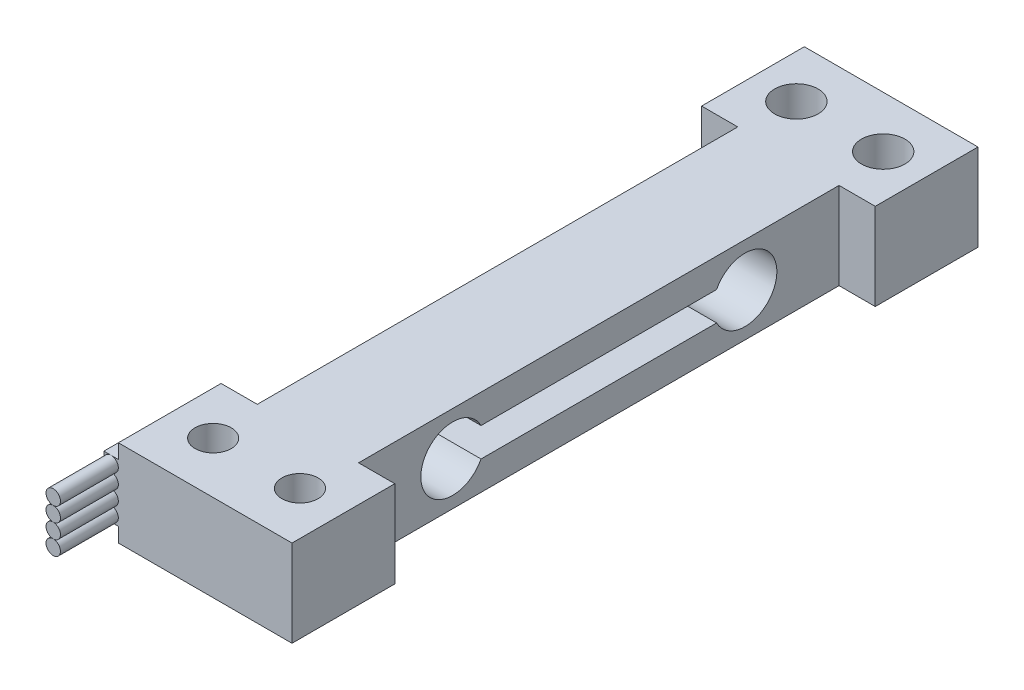
SolidWorks part; units mm, degrees
material "6063-O"
ref_plane "Front Plane" through (0, 0, 0) normal (0, 0, 1) x (1, 0, 0)
ref_plane "Top Plane" through (0, 0, 0) normal (0, 1, 0) x (1, 0, 0)
ref_plane "Right Plane" through (0, 0, 0) normal (1, 0, 0) x (0, 0, -1)
sketch "Sketch1" plane through (0, 0, 0) normal (0, 1, 0) x (1, 0, 0)
  line L0 (2.5, 7.1) -> (2.5, 40.3)
  line L1 (0, 0) -> (12, 0)
  line L2 (0, 0) -> (0, 7.1)
  line L3 (0, 7.1) -> (2.5, 7.1)
  line L4 (12, 0) -> (12, 7.1)
  line L5 (9.5, 7.1) -> (9.5, 40.3)
  line L6 (9.5, 40.3) -> (12, 40.3)
  line L7 (0, 40.3) -> (2.5, 40.3)
  line L8 (0, 40.3) -> (0, 47.4)
  line L9 (0, 47.4) -> (12, 47.4)
  line L10 (12, 40.3) -> (12, 47.4)
  line L11 (9.5, 7.1) -> (12, 7.1)
  point P13 (6, 0)
  dimension "D1" = 12
  dimension "D2" = 7.1
  dimension "D3" = 47.4
  dimension "D4" = 7
  dimension "D5" = 3.5
extrude "Boss-Extrude1" add sketch "Sketch1" along normal blind 6
sketch "Sketch2" plane through (0, 6, 0) normal (0, 1, 0) x (1, 0, 0)
  line L0 (12, 47.4) -> (0, 47.4) construction
  line L1 (0, 0) -> (12, 0) construction
  point P0 (3, 43.85)
  point P1 (9, 43.85)
  point P2 (9, 3.55)
  point P3 (3, 3.55)
  point P6 (6, 47.4)
  point P8 (6, 0)
  dimension "D1" = 6
  dimension "D2" = 3
  dimension "D3" = 3.55
  dimension "D4" = 6
  dimension "D5" = 3.55
  dimension "D6" = 3
hole_wizard "Ø3.0mm Dowel Hole1" positions "3DSketch1" profile "Sketch3" hole size "Ø3.0" standard "ISO" end condition through all
sketch3d "3DSketch1"
  point P0 (3, 6, -43.85)
  point P3 (9, 6, -43.85)
sketch "Sketch3" plane through (3, 6, -43.85) normal (1, 0, 0) x (0, 0, 1)
  line L0 (0, 0) -> (0, 6)
  line L1 (0, 6) -> (1.5, 6)
  line L2 (1.5, 6) -> (1.5, 0)
  line L5 (1.5, 0) -> (0, 0)
  line L11 (0, -6.35) -> (0, 107.95) construction
  dimension "Thru Hole Dia." = 3
  dimension "Thru Hole Depth" = 6
hole_wizard "Tap Drill for M3 Tap1" positions "3DSketch2" profile "Sketch4" hole size "M3" standard "ISO" end condition through all
sketch3d "3DSketch2"
  point P0 (9, 6, -3.55)
  point P3 (3, 6, -3.55)
sketch "Sketch4" plane through (9, 6, -3.55) normal (1, 0, 0) x (0, 0, 1)
  line L0 (0, 0) -> (0, 6)
  line L1 (0, 6) -> (1.25, 6)
  line L2 (1.25, 6) -> (1.25, 0)
  line L5 (1.25, 0) -> (0, 0)
  line L11 (0, -6.35) -> (0, 107.95) construction
  dimension "Thru Hole Dia." = 2.5
  dimension "Thru Hole Depth" = 6
sketch "Sketch5" plane through (0, 0, -47.4) normal (0, 0, -1) x (-1, 0, 0)
  line L0 (-6.75, 5) -> (-5.25, 5)
  line L1 (-5.25, 5) -> (-5.25, 2.68)
  line L2 (-5.25, 2.68) -> (-4, 2.68)
  line L3 (-4, 2.68) -> (-6, 1)
  line L4 (-6, 1) -> (-8, 2.68)
  line L5 (-8, 2.68) -> (-6.75, 2.68)
  line L6 (-6.75, 2.68) -> (-6.75, 5)
  line L7 (-12, 6) -> (0, 6) construction
  line L8 (-12, 0) -> (0, 0) construction
  point P8 (-6, 5)
  point P12 (-6, 6)
  dimension "D2" = 1
  dimension "D3" = 1.5
  dimension "D4" = 0.75
  dimension "D5" = 1.25
  dimension "D6" = 1.25
extrude "Boss-Extrude2" add sketch "Sketch5" along normal blind 0.25
sketch "Sketch6" plane through (9.5, 0, 0) normal (1, 0, 0) x (0, 0, -1)
  line L0 (47.4, 6) -> (47.4, 0) construction
  line L1 (0, 6) -> (0, 0) construction
  line L2 (15.5596, 4) -> (31.8404, 4)
  line L3 (15.5596, 2) -> (31.8404, 2)
  line L4 (7.1, 0) -> (40.3, 0) construction
  line L5 (7.1, 6) -> (40.3, 6) construction
  arc A0 (15.5596, 4) -> (15.5596, 2) centre (13.6, 3) ccw
  arc A1 (31.8404, 2) -> (31.8404, 4) centre (33.8, 3) ccw
  dimension "D1" = 4.4
  dimension "D2" = 13.6
  dimension "D3" = 13.6
  dimension "D4" = 2
  dimension "D5" = 2
extrude "Cut-Extrude1" cut sketch "Sketch6" against normal up to next
sketch "Sketch7" plane through (0, 0, 0) normal (-1, 0, 0) x (0, 0, 1)
  line L0 (0, 6) -> (0, 0) construction
  line L1 (0, 5) -> (-4.6, 5)
  line L2 (0, 5) -> (0, 1)
  line L3 (0, 1) -> (-4.6, 1)
  line L4 (-4.6, 5) -> (-4.6, 1)
  line L5 (-7.1, 6) -> (0, 6) construction
  line L6 (-7.1, 0) -> (0, 0) construction
  line L7 (-7.1, 6) -> (-7.1, 0) construction
  point P10 (-4.6, 3)
  dimension "D1" = 1
  dimension "D2" = 1
  dimension "D3" = 2.5
extrude "Boss-Extrude3" add sketch "Sketch7" along normal blind 1
sketch "Sketch8" plane through (0, 0, 0) normal (0, 0, 1) x (1, 0, 0)
  line L0 (-1, 1) -> (-1, 5) construction
  line L1 (-1, 5) -> (0, 5) construction
  circle A0 centre (-0.5, 4.5) radius 0.5
  circle A1 centre (-0.5, 3.5) radius 0.5
  circle A2 centre (-0.5, 2.5) radius 0.5
  circle A3 centre (-0.5, 1.5) radius 0.5
  dimension "D1" = 1
  dimension "D2" = 0.5
  dimension "D3" = 0.5
  dimension "D4" = 4
extrude "Boss-Extrude5" add sketch "Sketch8" along normal blind 4 separate body contours A0 | A1 | A2 | A3 region at (-0.5, 4.5, 0) region at (-0.5, 1.5, 0) region at (-0.5, 2.5, 0) region at (-0.5, 3.5, 0)
ref_plane "Plane1" through (6, 0, 0) normal (1, 0, 0) x (0, 0, -1)
ref_axis "Axis1" through (9, 0, -43.85) along (0, 1, 0)
ref_axis "Axis2" through (3, 0, -43.85) along (0, 1, 0)
ref_plane "Plane2" through (0, 0, -43.85) normal (0, 0, -1) x (-1, 0, 0)
ref_axis "Axis3" through (9, 0, -3.55) along (0, 1, 0)
ref_axis "Axis4" through (3, 0, -3.55) along (0, 1, 0)
